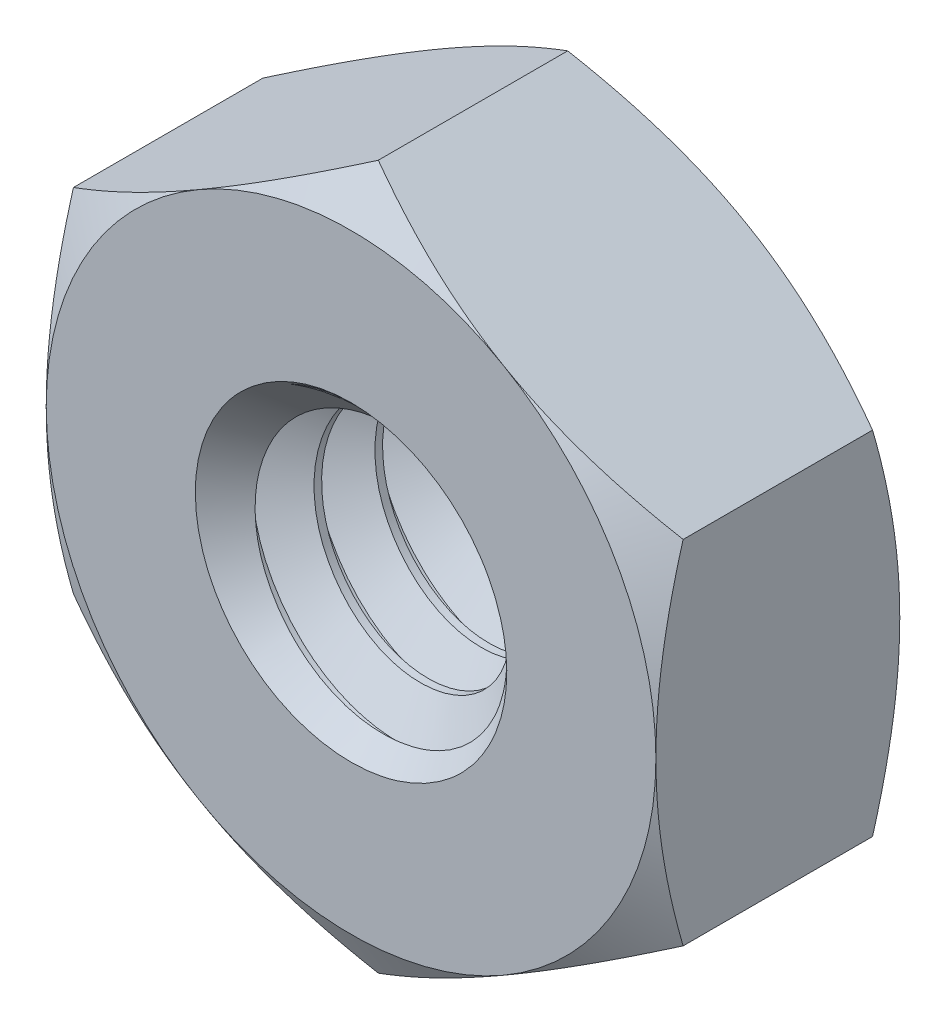
SolidWorks part; units mm, degrees
ref_plane "Front Plane" through (0, 0, 0) normal (0, 0, 1) x (1, 0, 0)
ref_plane "Top Plane" through (0, 0, 0) normal (0, 1, 0) x (1, 0, 0)
ref_plane "Right Plane" through (0, 0, 0) normal (1, 0, 0) x (0, 0, -1)
sketch "Sketch1" plane through (0, 0, 0) normal (1, 0, 0) x (0, 0, -1)
  line L0 (-0.8, 0) -> (0.8, 0) construction
  line L1 (-0.8, -2) -> (-0.8, 2) construction
  line L2 (0.8, -2) -> (0.8, 2) construction
  line L3 (-0.8, -1) -> (-0.8, 1) construction
  line L4 (-1.175, 1.0433) -> (-0.975, 0.6969) construction
  line L5 (-0.975, 0.6969) -> (-0.775, 1.0433) construction
  line L6 (-0.775, 1.0433) -> (-1.175, 1.0433) construction
  line L7 (-1.1625, 1.0217) -> (-0.7875, 1.0217) construction
  line L8 (-1.15, 1) -> (-0.8, 1) construction
  line L9 (-1, 0.7402) -> (-0.95, 0.7402) construction
  line L10 (-0.975, 0.7402) -> (-0.975, 0.6969) construction
  line L11 (-0.975, 1.0433) -> (-0.975, 1) construction
  point P4 (0, 0)
  point P7 (-0.8, 0)
  point P11 (0.8, 0)
  point P14 (-0.8, 0)
  point P26 (-0.975, 1.0217)
  point P27 (-0.8, -1)
  dimension "Height" = 1.6
  dimension "Width" = 4
  dimension "Thread OD" = 2
  dimension "D1" = 60
  dimension "Pitch" = 0.4
  dimension "D2" = 0.05
sketch "Sketch2" plane through (0, 0, 0) normal (0, 0, 1) x (1, 0, 0)
  line L1 (0, 2.3094) -> (-2, 1.1547)
  line L2 (-2, 1.1547) -> (-2, -1.1547)
  line L3 (-2, -1.1547) -> (0, -2.3094)
  line L4 (0, -2.3094) -> (2, -1.1547)
  line L5 (2, -1.1547) -> (2, 1.1547)
  line L6 (2, 1.1547) -> (0, 2.3094)
  circle A0 centre (0, 0) radius 2 construction
  circle A1 centre (0, 0) radius 1
extrude "Boss-Extrude1" add sketch "Sketch2" along normal up to vertex (0.8 mm away) and the other way up to vertex (0.8 mm away) up to point (0, -2, 0.8) other way up to point (0, -2, -0.8)
sketch "Sketch3" plane through (0, 0, 0.8) normal (0, 0, 1) x (1, 0, 0)
  circle A0 centre (0, 0) radius 2
extrude "Cut-Extrude1" cut sketch "Sketch3" against normal through all draft 60 flip side to cut
mirror "Mirror1" about plane through (0, 0, 0) normal (0, 0, 1) of "Cut-Extrude1"
ref_axis "Center Axis 1" through (0, 0, -10.9016) along (0, 0, 1)
ref_plane "Contact Plane 1" through (0, 0, 0.8) normal (0, 0, 1) x (1, 0, 0)
ref_plane "Contact Plane 2" through (0, 0, -0.8) normal (0, 0, -1) x (-1, 0, 0)
sketch "Sketch4" plane through (0, 0, 0) normal (1, 0, 0) x (0, 0, -1)
  line L1 (-1.1625, 1.0217) -> (-1, 0.7402)
  line L2 (-1, 0.7402) -> (-0.95, 0.7402)
  line L3 (-0.95, 0.7402) -> (-0.7875, 1.0217)
  line L4 (-1.1625, 1.0217) -> (-0.7875, 1.0217) construction
  line L5 (-1.1625, 1.0217) -> (-0.7875, 1.0217)
sketch "Sketch5" plane through (0, 0, 0.8) normal (0, 0, 1) x (1, 0, 0)
  circle A0 centre (0, 0) radius 1 construction
  circle A1 centre (0, 0) radius 1
curve "Helix/Spiral1" pitch 0.4 height 2 radius 1 centre (0, 0, 0.8) axis (0, 0, -1) start towards (0, 1, 0)
sweep "Sweep1" add profiles "Sketch4" path "Helix/Spiral1"
sketch "Sketch6" plane through (0, 0, 0.8) normal (0, 0, 1) x (1, 0, 0)
  circle A1 centre (0, 0) radius 1.0217
extrude "Cut-Extrude2" cut sketch "Sketch6" along normal through all and the other way through all draft 45
sketch "Sketch7" plane through (0, 0, -0.8) normal (0, 0, -1) x (-1, 0, 0)
  circle A1 centre (0, 0) radius 1.0217
  circle A2 centre (0, 0) radius 1.0217
  dimension "D1" = 0
extrude "Cut-Extrude3" cut sketch "Sketch7" along normal through all and the other way through all draft 45
sketch "Sketch8" plane through (0, 0, 0) normal (0, 0, 1) x (1, 0, 0)
  line L0 (0, 2.3094) -> (0, -2.3094)
  dimension "D1" = 4.6188
equation "\"D2@Sketch1\"=\"Pitch@Sketch1\"/8"
equation "\"D4@Helix/Spiral1\"=\"Pitch@Sketch1\""
equation "\"D3@Helix/Spiral1\"=\"Height@Sketch1\"+\"Pitch@Sketch1\""
